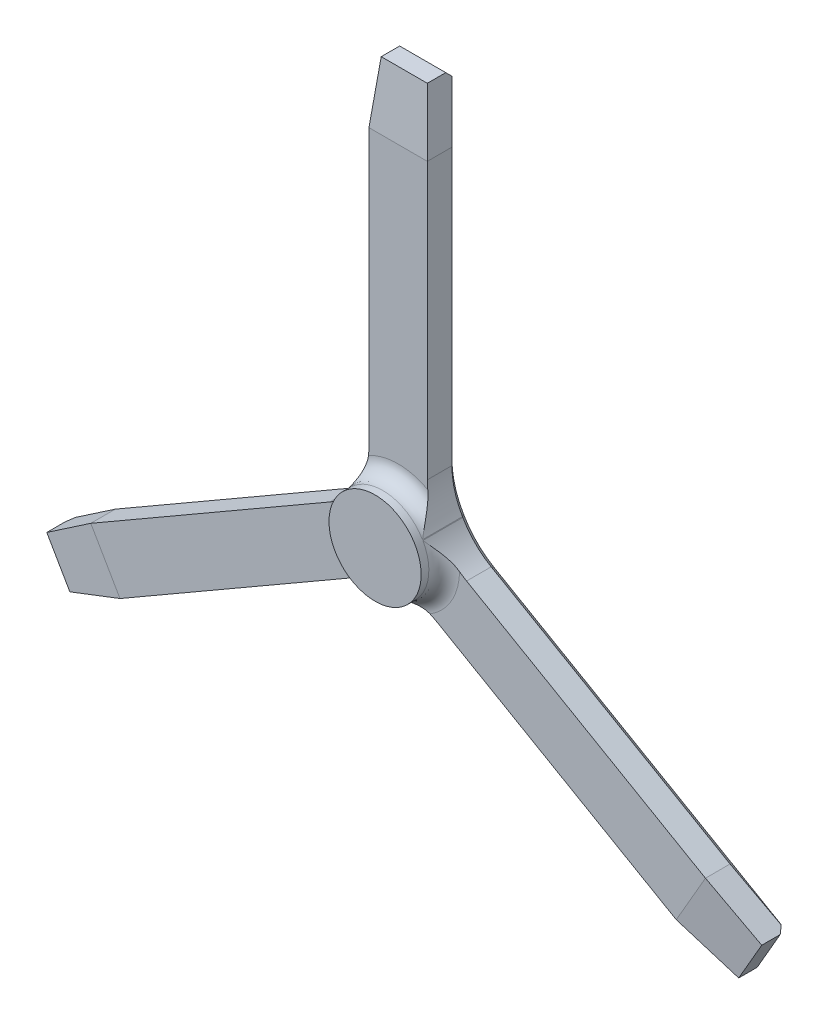
SolidWorks part; units mm, degrees
ref_plane "Front Plane" through (0, 0, 0) normal (0, 0, 1) x (1, 0, 0)
ref_plane "Top Plane" through (0, 0, 0) normal (0, 1, 0) x (1, 0, 0)
ref_plane "Right Plane" through (0, 0, 0) normal (1, 0, 0) x (0, 0, -1)
sketch "Sketch1" plane through (0, 0, 0) normal (0, 0, 1) x (1, 0, 0)
  line L0 (-1.9, 24) -> (1.9, 24) construction
  line L1 (0, 0) -> (0, 24) construction
  line L2 (-1.9, 24) -> (-1.9, 26)
  line L3 (-1.9, 26) -> (1.9, 26)
  line L4 (1.9, 26) -> (1.9, 24)
  line L5 (23.4667, -11.3546) -> (21.5667, -14.6454)
  line L6 (21.5667, -14.6454) -> (19.8346, -13.6454)
  line L7 (21.7346, -10.3546) -> (23.4667, -11.3546)
  line L8 (-21.5667, -14.6454) -> (-23.4667, -11.3546)
  line L9 (-23.4667, -11.3546) -> (-21.7346, -10.3546)
  line L10 (-19.8346, -13.6454) -> (-21.5667, -14.6454)
  line L11 (0, 0) -> (1.9, 24) construction
  line L12 (0, 0) -> (19.8346, -13.6454) construction
  line L13 (-1.9, 24) -> (-1.9, 1.097)
  line L14 (-1.9, 1.097) -> (-21.7346, -10.3546)
  line L15 (-19.8346, -13.6454) -> (0, -2.1939)
  line L16 (0, -2.1939) -> (19.8346, -13.6454)
  line L17 (21.7346, -10.3546) -> (1.9, 1.097)
  line L18 (1.9, 1.097) -> (1.9, 24)
  circle A0 centre (0, 0) radius 24 construction
  dimension "D1" = 48
  dimension "D2" = 3.8
  dimension "D3" = 2
  dimension "D4" = 120
  dimension "D5" = 24.0751
  dimension "D6" = 3
extrude "Boss-Extrude1" add sketch "Sketch1" along normal blind 2 contours L18 A0 L13 L14 L15 L16 L17 region at (0, 0, 0)
chamfer "Chamfer1" distance 4 distance2 0.4 3 edges at (22.5167, -13, 2) (-22.5167, -13, 2) (0, 26, 2) first distance on face at (0, 0, 2)
chamfer "Chamfer2" distance 0.4 distance2 4 3 edges at (23.4667, -11.3546, 0.8) (-1.9, 26, 0.8) (-21.5667, -14.6454, 0.8) first distance on face at (22.5167, -13, 0.8) first distance on face at (0, 26, 0.8) first distance on face at (-22.5167, -13, 0.8)
chamfer "Chamfer3" distance 4 distance2 0.4 3 edges at (1.9, 26, 0.8) (21.5667, -14.6454, 0.8) (-23.4667, -11.3546, 0.8) first distance on face at (1.9, 15.2388, 1.12) first distance on face at (12.2472, -9.2648, 1.12) first distance on face at (-14.1472, -5.9739, 1.12)
sketch "Sketch2" plane through (0, 0, 0) normal (0, 0, -1) x (-1, 0, 0)
  circle A0 centre (0, 0) radius 3
  dimension "D1" = 6
extrude "Boss-Extrude2" add sketch "Sketch2" against normal blind 3.5
fillet "Fillet1" radius 5 6 edges at (1.9, 2.3216, 1) (2.9606, 0.4846, 1) (1.0606, -2.8063, 1) (-1.0606, -2.8063, 1) (-2.9606, 0.4846, 1) (-1.9, 2.3216, 1)
fillet "Fillet2" radius 1 3 edges at (0, 3, 2) (2.5981, -1.5, 2) (-2.5981, -1.5, 2)
chamfer "Chamfer4" distance 0.4 angle 45 18 edges at (22.5167, -13, 0) (-22.5167, -13, 0) (0, 26, 0) (12.2293, -4.8667, 0) (3.4082, 0.4282, 0) (2.5981, 1.5, 0) (2.0749, 2.7374, 0) (1.9, 13.0242, 0) (-12.2293, -4.8667, 0) (-3.4082, 0.4282, 0) (-2.5981, 1.5, 0) (-2.0749, 2.7374, 0) (-1.9, 13.0242, 0) (10.3293, -8.1576, 0) (1.3332, -3.1657, 0) (0, -3, 0) (-1.3332, -3.1657, 0) (-10.3293, -8.1576, 0)
